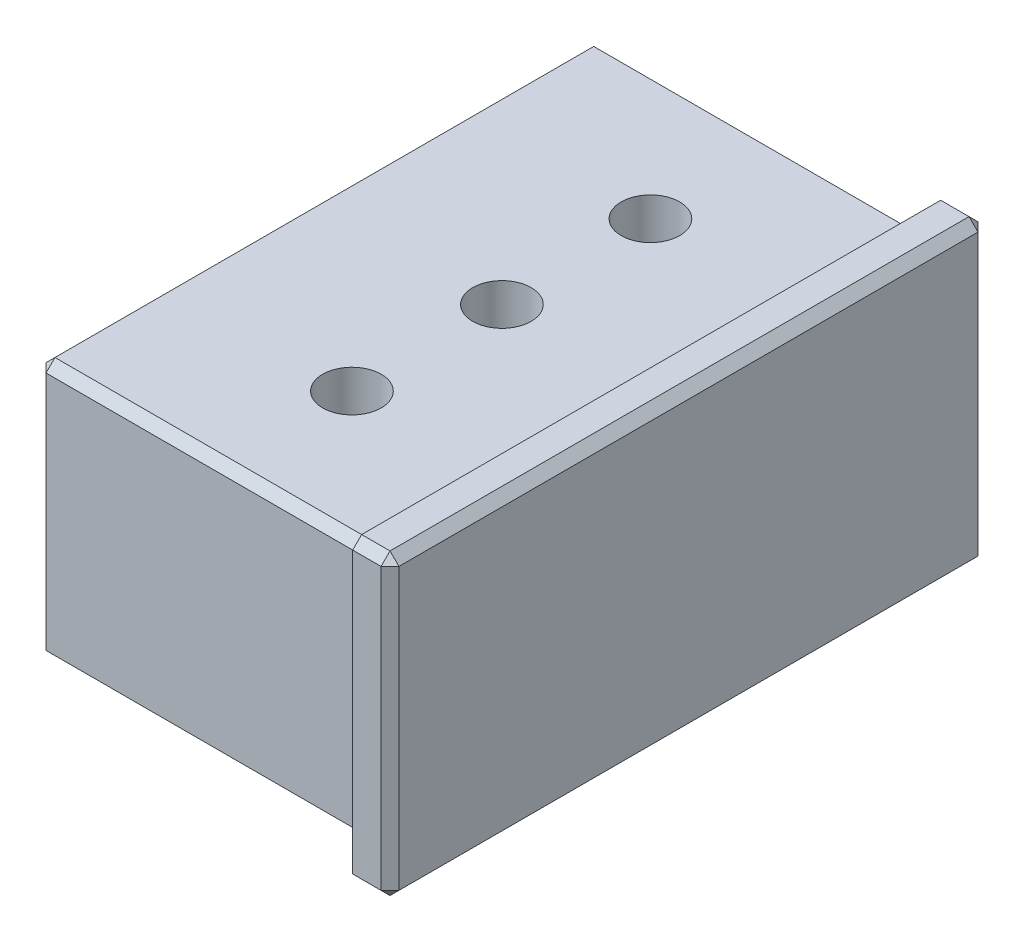
SolidWorks part; units mm, degrees
material "PET"
ref_plane "Front Plane" through (0, 0, 0) normal (0, 0, 1) x (1, 0, 0)
ref_plane "Top Plane" through (0, 0, 0) normal (0, 1, 0) x (1, 0, 0)
ref_plane "Right Plane" through (0, 0, 0) normal (1, 0, 0) x (0, 0, -1)
sketch "Sketch1" plane through (0, 0, 0) normal (1, 0, 0) x (0, 0, -1)
  line L1 (0, 0) -> (47.371, 0)
  line L2 (0, 0) -> (0, 21.971)
  line L3 (0, 21.971) -> (47.371, 21.971)
  line L4 (47.371, 0) -> (47.371, 21.971)
  dimension "D1" = 21.971
  dimension "D2" = 47.371
extrude "Boss-Extrude1" add sketch "Sketch1" along normal blind 28.575
sketch "Sketch2" plane through (28.575, 0, 0) normal (1, 0, 0) x (0, 0, -1)
  line L0 (0, 21.971) -> (47.371, 0) construction
  line L1 (0, 0) -> (47.371, 21.971) construction
  line L9 (49.0855, -1.7145) -> (-1.7145, -1.7145)
  line L10 (49.0855, -1.7145) -> (49.0855, 23.6855)
  line L11 (49.0855, 23.6855) -> (-1.7145, 23.6855)
  line L12 (-1.7145, -1.7145) -> (-1.7145, 23.6855)
  line L13 (49.0855, -1.7145) -> (-1.7145, 23.6855) construction
  line L14 (49.0855, 23.6855) -> (-1.7145, -1.7145) construction
  point P0 (23.6855, 10.9855)
  point P9 (23.6855, 10.9855)
  dimension "D1" = 50.8
  dimension "D2" = 25.4
extrude "Boss-Extrude2" add sketch "Sketch2" along normal blind 3.175
chamfer "Chamfer1" distance 0.762 angle 45 16 edges at (31.75, 23.6855, -23.6855) (30.1625, 23.6855, -49.0855) (31.75, 10.9855, -49.0855) (30.1625, -1.7145, -49.0855) (31.75, -1.7145, -23.6855) (30.1625, -1.7145, 1.7145) (31.75, 10.9855, 1.7145) (30.1625, 23.6855, 1.7145) (0, 0, -23.6855) (14.2875, 0, -47.371) (0, 10.9855, -47.371) (14.2875, 21.971, -47.371) (0, 21.971, -23.6855) (14.2875, 21.971, 0) (0, 10.9855, 0) (14.2875, 0, 0)
sketch "Sketch3" plane through (0, 21.971, 0) normal (0, 1, 0) x (1, 0, 0)
  circle A0 centre (15.875, 23.6855) radius 2.4892
  circle A1 centre (15.875, 36.322) radius 2.4892
  circle A2 centre (15.875, 10.922) radius 2.4892
  point P6 (15.875, 36.322)
  point P7 (15.875, 36.322)
  point P9 (15.875, 23.6855)
  point P11 (15.875, 10.922)
  dimension "D1" = 4.9784
extrude "Cut-Extrude1" cut sketch "Sketch3" against normal through all
equation "\"D1@Sketch1\"=1-2*0.065-0.005"
equation "\"D2@Sketch1\"=2-2*0.065-0.005"
